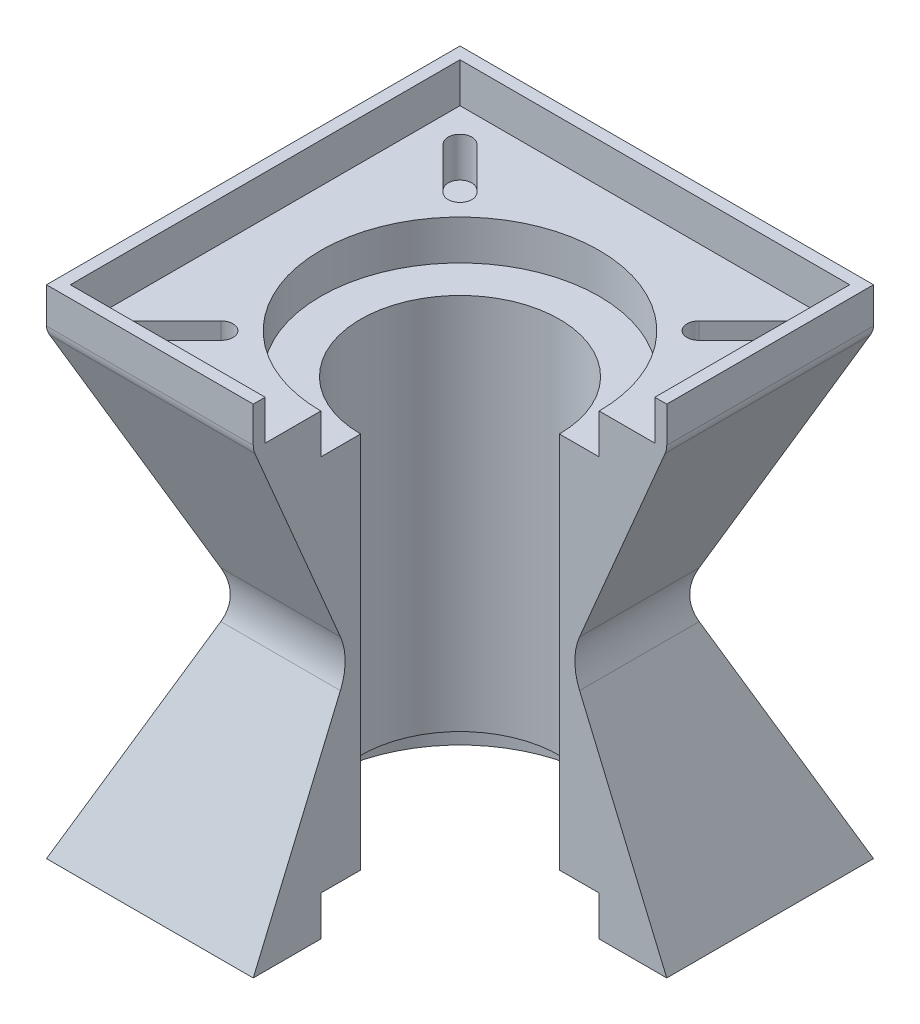
SolidWorks part; units mm, degrees
material "Cast Stainless Steel"
ref_plane "Front Plane" through (0, 0, 0) normal (0, 0, 1) x (1, 0, 0)
ref_plane "Top Plane" through (0, 0, 0) normal (0, 1, 0) x (1, 0, 0)
ref_plane "Right Plane" through (0, 0, 0) normal (1, 0, 0) x (0, 0, -1)
sketch "Sketch1" plane through (0, 0, 0) normal (0, 1, 0) x (1, 0, 0)
  line L1 (-52, 52) -> (52, 52)
  line L2 (-52, 52) -> (-52, -52)
  line L3 (-52, -52) -> (52, -52)
  line L4 (52, 52) -> (52, -52)
  line L5 (-52, 52) -> (52, -52) construction
  line L6 (-52, -52) -> (52, 52) construction
  point P0 (0, 0)
  dimension "D1" = 104
extrude "Boss-Extrude3" add sketch "Sketch1" along normal blind 57.5 draft 23
mirror "Mirror1" about plane through (0, 57.5, 0) normal (0, 1, 0) of bodies 103
sketch "Sketch2" plane through (0, 115, 0) normal (0, 1, 0) x (1, 0, 0)
  circle A0 centre (0, 0) radius 25
  dimension "D1" = 50
extrude "Cut-Extrude1" cut sketch "Sketch2" against normal through all
fillet "Fillet1" radius 15 4 edges at (-27.5927, 57.5, 0) (0, 57.5, -27.5927) (27.5927, 57.5, 0) (0, 57.5, 27.5927)
sketch "Sketch3" plane through (0, 115, 0) normal (0, 1, 0) x (1, 0, 0)
  circle A0 centre (0, 0) radius 35
  dimension "D1" = 70
extrude "Cut-Extrude2" cut sketch "Sketch3" against normal blind 10
ref_plane "Plane1" through (0, 57.5, 0) normal (0, 1, 0) x (1, 0, 0)
mirror "Mirror2" about plane through (0, 57.5, 0) normal (0, 1, 0) of "Cut-Extrude2"
sketch "Sketch4" plane through (0, 115, 0) normal (0, 1, 0) x (1, 0, 0)
  line L1 (0, 0) -> (52, 0)
  line L2 (0, 0) -> (0, -52)
  line L3 (0, -52) -> (52, -52)
  line L4 (52, 0) -> (52, -52)
extrude "Cut-Extrude3" cut sketch "Sketch4" against normal through all
sketch "Sketch5" plane through (0, 115, 0) normal (0, 1, 0) x (1, 0, 0)
  line L6 (-52, -52) -> (0, -52)
  line L7 (0, -52) -> (0, -35)
  line L8 (35, 0) -> (52, 0)
  line L9 (52, 0) -> (52, 52)
  line L10 (52, 52) -> (-52, 52)
  line L11 (-52, 52) -> (-52, -52)
  line L12 (-52, -52) -> (0, -52)
  line L13 (0, -52) -> (0, -49)
  line L14 (49, 0) -> (52, 0)
  line L15 (52, 0) -> (52, 52)
  line L16 (52, 52) -> (-52, 52)
  line L17 (-52, 52) -> (-52, -52)
  line L24 (-49, -49) -> (-3, -49)
  line L25 (-3, -49) -> (-3, -37.8814)
  line L26 (37.8814, 3) -> (49, 3)
  line L27 (49, 3) -> (49, 49)
  line L28 (49, 49) -> (-49, 49)
  line L29 (-49, 49) -> (-49, -49)
  line L30 (-49, -49) -> (0, -49)
  line L33 (49, 0) -> (49, 49)
  line L34 (49, 49) -> (-49, 49)
  line L35 (-49, 49) -> (-49, -49)
  arc A1 (35, 0) -> (0, -35) centre (0, 0) ccw
  arc A4 (37.8814, 3) -> (-3, -37.8814) centre (0, 0) ccw
  dimension "D1" = 0
  dimension "D2" = 3
extrude "Boss-Extrude4" add sketch "Sketch5" along normal blind 10
fillet "Fillet2" radius 5 1 edges at (-26, 115, 52)
fillet "Fillet3" radius 5 3 edges at (52, 115, -26) (0, 115, -52) (-52, 115, -0.0523)
sketch "Sketch6" plane through (0, 115, 0) normal (0, 1, 0) x (1, 0, 0)
  line L0 (0, 0) -> (-52, 52) construction
  line L1 (-40.6586, 40.6586) -> (-30.052, 30.052) construction
  line L2 (-38.5373, 42.78) -> (-27.9307, 32.1734)
  line L3 (-42.78, 38.5373) -> (-32.1734, 27.9307)
  circle A0 centre (0, 0) radius 50 construction
  arc A1 (-38.5373, 42.78) -> (-42.78, 38.5373) centre (-40.6586, 40.6586) ccw
  arc A2 (-32.1734, 27.9307) -> (-27.9307, 32.1734) centre (-30.052, 30.052) ccw
  point P7 (-35.3553, 35.3553)
  dimension "D1" = 100
  dimension "D3" = 3
  dimension "D2" = 15
extrude "Cut-Extrude4" cut sketch "Sketch6" against normal blind 10
pattern_circular "CirPattern1" count 4 over 360 about axis through (0, 115, 0) along (0, 1, 0) of "Cut-Extrude4"
equation "\"a\"= 115"
equation "\"b\"= 104"
equation "\"c\"= 23"
